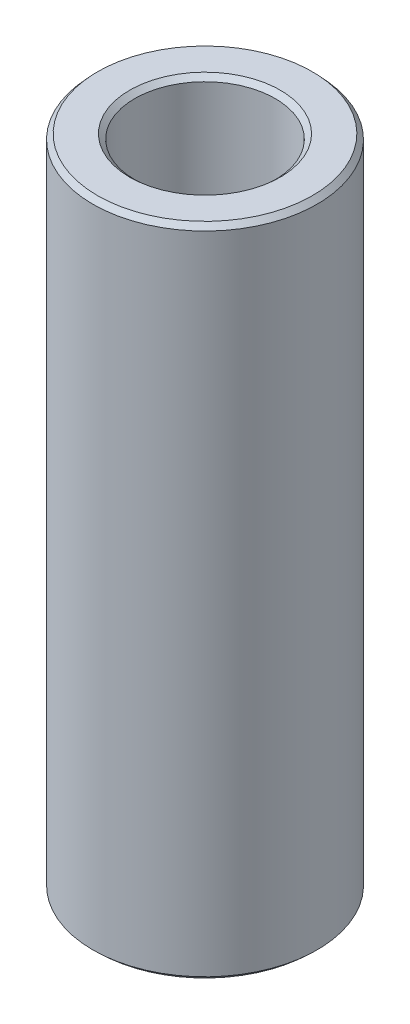
SolidWorks part; units mm, degrees
ref_plane "Front Plane" through (0, 0, 0) normal (0, 0, 1) x (1, 0, 0)
ref_plane "Top Plane" through (0, 0, 0) normal (0, 1, 0) x (1, 0, 0)
ref_plane "Right Plane" through (0, 0, 0) normal (1, 0, 0) x (0, 0, -1)
sketch "Sketch1" plane through (0, 0, 0) normal (0, 1, 0) x (1, 0, 0)
  circle A0 centre (0, 0) radius 20
  dimension "SLEEVE_OD" = 40
extrude "Boss-Extrude1" add sketch "Sketch1" along normal blind 116.9878
sketch "Sketch2" plane through (0, 0, 0) normal (0, 1, 0) x (1, 0, 0)
  circle A0 centre (0, 0) radius 12.5388
  dimension "BORE_D" = 25.0775
extrude "Cut-Extrude1" cut sketch "Sketch2" along normal through all
chamfer "Chamfer1" distance 0.9097 angle 42.6 4 edges at (0, 116.9878, 12.5388) (0, 0, 12.5388) (0, 0, 20) (0, 116.9878, 20) first distance on face at (0, 116.9878, 12.5388) first distance on face at (0, 0, 12.5388) first distance on face at (0, 116.9878, 20)
